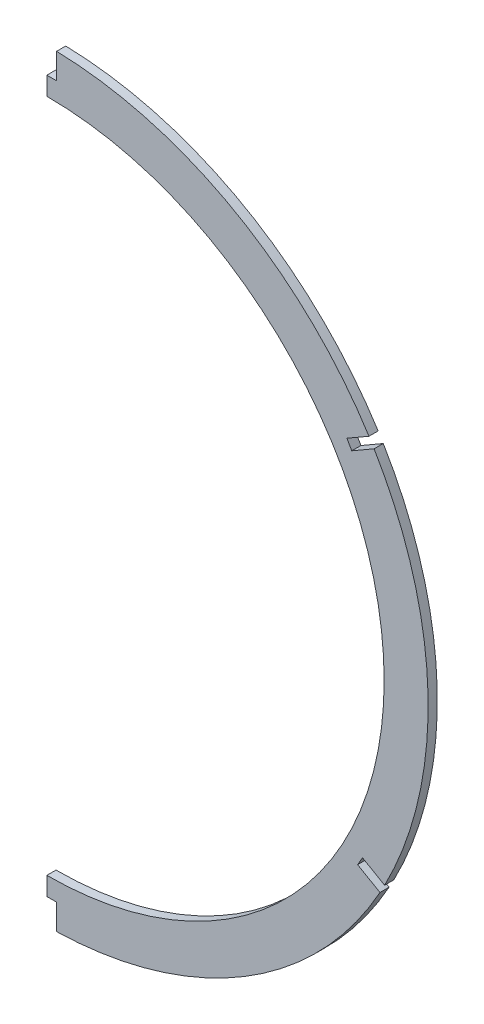
SolidWorks part; units mm, degrees
material "Balsa"
ref_plane "Front Plane" through (0, 0, 0) normal (0, 0, 1) x (1, 0, 0)
ref_plane "Top Plane" through (0, 0, 0) normal (0, 1, 0) x (1, 0, 0)
ref_plane "Right Plane" through (0, 0, 0) normal (1, 0, 0) x (0, 0, -1)
sketch "Sketch2" plane through (0, 0, 0) normal (0, 0, 1) x (1, 0, 0)
  line L0 (0, 0) -> (0, 236.6718) construction
  line L1 (-1.651, 128.5137) -> (-1.651, 121.4017) construction
  line L3 (1.651, 128.5137) -> (1.651, 121.4017) construction
  line L4 (-1.651, 121.4017) -> (1.651, 121.4017) construction
  line L5 (-136.2041, -77.9016) -> (0, 0.7359) construction
  line L6 (-136.2041, -77.9016) -> (0, 0.7359) construction
  line L7 (136.2041, -77.9016) -> (0, 0.7359) construction
  line L8 (136.2041, -77.9016) -> (0, 0.7359) construction
  line L9 (-116.9741, -64.8927) -> (-110.0155, -60.8752) construction
  line L10 (-115.4036, -67.7988) -> (-108.3645, -63.7348) construction
  line L11 (-110.0155, -60.8752) -> (-108.3645, -63.7348) construction
  line L12 (-117.55, -65.2252) -> (-116.9741, -64.8927) construction
  line L13 (-115.899, -68.0849) -> (-115.4036, -67.7988) construction
  line L14 (115.4036, -67.7988) -> (109.2442, -64.2427) construction
  line L15 (110.8952, -61.3831) -> (109.2442, -64.2427) construction
  line L16 (116.9741, -64.8927) -> (110.8952, -61.3831) construction
  arc A0 (-1.651, 128.5137) -> (-116.9741, -64.8927) centre (0, -3.556) ccw
  arc A1 (0.0665, 128.1531) -> (63.0696, -118.8475) centre (0, -3.3993) ccw construction
  circle A2 centre (0, -3.556) radius 116.84
  arc A3 (63.0696, -118.8475) -> (0.0665, 128.1531) centre (0, -3.3993) ccw construction
  arc A4 (0, 128.524) -> (-1.651, 128.5137) centre (0, -3.556) ccw
  circle A5 centre (0, -3.556) radius 132.08 construction
  arc A6 (1.651, 128.5137) -> (0, 128.524) centre (0, -3.556) ccw
  arc A7 (-116.9741, -64.8927) -> (-116.1978, -66.3509) centre (0, -3.556) ccw
  arc A8 (-115.4036, -67.7988) -> (115.4036, -67.7988) centre (0, -3.556) ccw
  arc A9 (-116.1978, -66.3509) -> (-115.4036, -67.7988) centre (0, -3.556) ccw
  arc A10 (115.4036, -67.7988) -> (116.1978, -66.3509) centre (0, -3.556) ccw
  arc A11 (116.9741, -64.8927) -> (1.651, 128.5137) centre (0, -3.556) ccw
  arc A12 (116.1978, -66.3509) -> (116.9741, -64.8927) centre (0, -3.556) ccw
  point P24 (-115.4036, -67.7988)
  dimension "D1" = 3.556
  dimension "D3" = 264.16
  dimension "D2" = 15.24
  dimension "D4" = 3.302
  dimension "D5" = 7.112
  dimension "D6" = 3.302
  dimension "D7" = 8.128
  dimension "D8" = 7.076
extrude "Boss-Extrude1" add sketch "Sketch2" along normal mid plane 3.175
sketch "Sketch3" plane through (0, 0, 0) normal (1, 0, 0) x (0, 0, -1)
  line L1 (-109.3908, 192.564) -> (122.8198, 192.564)
  line L2 (-109.3908, 192.564) -> (-109.3908, -206.3906)
  line L3 (-109.3908, -206.3906) -> (122.8198, -206.3906)
  line L4 (122.8198, 192.564) -> (122.8198, -206.3906)
extrude "Cut-Extrude1" cut sketch "Sketch3" against normal through all
sketch "Sketch4" plane through (0, 0, 1.5875) normal (0, 0, 1) x (1, 0, 0)
  line L0 (0, 0) -> (0, 113.284) construction
  line L1 (0, 113.284) -> (0, 119.634) construction
  line L2 (-99.2768, 58.0533) -> (-104.776, 61.2283) construction
  line L3 (3.3782, 119.634) -> (-3.3782, 119.634)
  line L4 (0, 119.634) -> (0, 129.794)
  line L5 (3.3782, 129.794) -> (-3.3782, 129.794)
  line L6 (-3.3782, 119.634) -> (-3.3782, 129.794)
  line L7 (-105.6206, 59.7655) -> (-103.9315, 62.6911)
  line L8 (7.6459, 0.7359) -> (-7.6459, 0.7359) construction
  line L9 (-103.9315, 62.6911) -> (-112.7303, 67.7711)
  line L10 (102.9936, -58.7275) -> (108.4929, -61.9025) construction
  line L11 (-130.6719, 76.1793) -> (0, 0.7359) construction
  line L12 (-112.7303, 67.7711) -> (-114.4194, 64.8455)
  line L13 (-130.6719, -74.7076) -> (0, 0.7359) construction
  line L14 (0, 0.7359) -> (0, -120.396) construction
  line L15 (0, -120.396) -> (0, -126.746) construction
  line L16 (0, 128.524) -> (0, 113.284) construction
  line L17 (-102.9936, -58.7275) -> (-108.4929, -61.9025) construction
  line L18 (3.3782, -126.746) -> (-3.3782, -126.746)
  line L19 (0, -126.746) -> (0, -136.906)
  line L20 (3.3782, -136.906) -> (-3.3782, -136.906)
  line L21 (-3.3782, -126.746) -> (-3.3782, -136.906)
  line L22 (-107.6483, -63.3653) -> (-109.3374, -60.4397)
  line L23 (-109.3374, -60.4397) -> (-118.1363, -65.5197)
  line L24 (-118.1363, -65.5197) -> (-116.4472, -68.4453)
  line L25 (-107.6483, -63.3653) -> (-116.4472, -68.4453)
  line L26 (-105.6206, 59.7655) -> (-114.4194, 64.8455)
  line L27 (130.6719, -74.7076) -> (0, 0.7359) construction
  line L28 (130.6719, 76.1793) -> (0, 0.7359) construction
  line L29 (99.2768, 58.0533) -> (104.776, 61.2283) construction
  line L30 (105.6206, 59.7655) -> (114.4194, 64.8455)
  line L31 (107.6483, -63.3653) -> (116.4472, -68.4453)
  line L32 (118.1363, -65.5197) -> (116.4472, -68.4453)
  line L33 (109.3374, -60.4397) -> (118.1363, -65.5197)
  line L34 (107.6483, -63.3653) -> (109.3374, -60.4397)
  line L35 (3.3782, -126.746) -> (3.3782, -136.906)
  line L36 (112.7303, 67.7711) -> (114.4194, 64.8455)
  line L37 (103.9315, 62.6911) -> (112.7303, 67.7711)
  line L38 (105.6206, 59.7655) -> (103.9315, 62.6911)
  line L39 (3.3782, 119.634) -> (3.3782, 129.794)
  point P18 (-102.9936, -58.7275)
  point P23 (-99.2768, 58.0533)
  point P30 (-117.2917, -66.9825)
  point P32 (-113.5748, 66.3083)
  point P53 (113.5748, 66.3083)
  point P54 (117.2917, -66.9825)
  point P55 (99.2768, 58.0533)
  point P56 (102.9936, -58.7275)
  arc M6 (0, -135.636) -> (0, 128.524) centre (0, -3.556) ccw
  line M7 (0, 128.524) -> (0, 113.284)
  line M9 (0, -120.396) -> (0, -135.636)
  dimension "D1" = 113.284
  dimension "D2" = 6.35
  dimension "D3" = 10.16
  dimension "D4" = 3.3782
  dimension "D5" = 0.7359
  dimension "D6" = 60
  dimension "D7" = 121.1319
  dimension "D8" = 6.35
  dimension "D9" = 10.16
  dimension "D10" = 3.3782
  dimension "D11" = 118.9268
  dimension "D12" = 6.35
  dimension "D13" = 10.16
  dimension "D14" = 1.6891
  dimension "D15" = 114.6349
  dimension "D16" = 6.35
  dimension "D17" = 1.6891
  dimension "D18" = 10.16
extrude "Cut-Extrude2" cut sketch "Sketch4" against normal through all contours L3 L39 M6 M7 | L38 L30 L37 M6 | L34 L31 L33 M6 | L35 L18 M9 M6 region at (1.6877, -131.1838, 1.5875) region at (112.3423, -64.1285, 1.5875) region at (108.6284, 63.4491, 1.5875) region at (1.6877, 124.0718, 1.5875)
